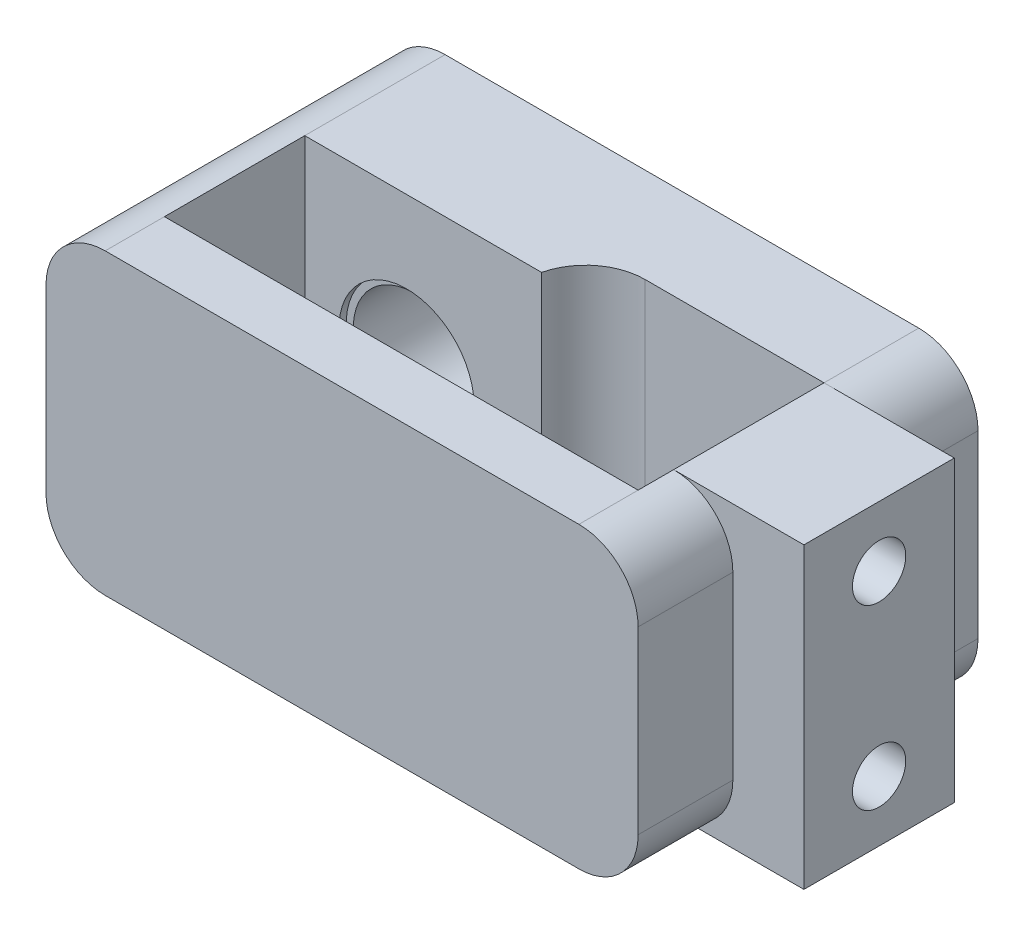
SolidWorks part; units mm, degrees
ref_plane "Front Plane" through (0, 0, 0) normal (0, 0, 1) x (1, 0, 0)
ref_plane "Top Plane" through (0, 0, 0) normal (0, 1, 0) x (1, 0, 0)
ref_plane "Right Plane" through (0, 0, 0) normal (1, 0, 0) x (0, 0, -1)
sketch "Sketch1" plane through (0, 0, 0) normal (0, 1, 0) x (1, 0, 0)
  line L1 (-20, 2.5) -> (20, 2.5)
  line L2 (-20, 2.5) -> (-20, -9.35)
  line L3 (-20, -9.35) -> (20, -9.35)
  line L4 (20, 2.5) -> (20, -9.35)
  line L7 (-25, 14.35) -> (25, 14.35)
  line L8 (-25, 14.35) -> (-25, -14.35)
  line L9 (-25, -14.35) -> (25, -14.35)
  line L10 (25, 14.35) -> (25, -14.35)
  point P0 (0, 0)
  point P6 (0, -9.35)
  point P7 (0, 0)
  point P12 (0, -14.35)
  point P13 (25, 0)
  dimension "D1" = 5
  dimension "D2" = 11.85
  dimension "D3" = 50
  dimension "D4" = 28.7
  dimension "D5" = 5
extrude "Boss-Extrude1" add sketch "Sketch1" along normal blind 25.2
sketch "Sketch4" plane through (0, 0, -2.5) normal (0, 0, 1) x (1, 0, 0)
  line L0 (-25, 25.2) -> (-25, 0) construction
  point P0 (-11.4, 12.6)
  point P7 (-25, 12.6)
  dimension "D1" = 13.6
sketch "Sketch9" plane through (20, 0, 0) normal (-1, 0, 0) x (0, 0, 1)
  line L0 (0, 20.1) -> (0, 5.1) construction
  line L2 (14.35, 25.2) -> (14.35, 0) construction
  point P0 (0, 20.1)
  point P2 (0, 5.1)
  point P11 (14.35, 12.6)
  point P12 (0, 12.6)
  dimension "D1" = 15
hole_wizard "Hole1" positions "Sketch4" profile "Sketch3" legacy end condition up to next
sketch "Sketch3" plane through (-11.4, 12.6, -2.5) normal (1, 0, 0) x (0, -1, 0)
  line L0 (0, 0) -> (0, 11.85)
  line L1 (0, 11.85) -> (5.1, 11.85)
  line L2 (5.1, 11.85) -> (5.1, 0.6)
  line L3 (5.1, 0.6) -> (5.7, 0.6)
  line L4 (5.7, 0.6) -> (5.7, 0)
  line L5 (5.7, 0) -> (0, 0)
  line L6 (0, 110) -> (0, -10) construction
  dimension "Diameter" = 10.2
  dimension "Depth" = 11.85
  dimension "C-Bore Diameter" = 11.4
  dimension "C-Bore Depth" = 0.6
sketch "Sketch10" plane through (25, 0, 0) normal (1, 0, 0) x (0, 0, -1)
  line L0 (-14.35, 25.2) -> (14.35, 25.2) construction
  line L1 (-6.35, 25.2) -> (6.35, 25.2)
  line L2 (-6.35, 25.2) -> (-6.35, 0)
  line L3 (-6.35, 0) -> (6.35, 0)
  line L4 (6.35, 25.2) -> (6.35, 0)
  line L5 (-14.35, 0) -> (14.35, 0) construction
  point P8 (0, 0)
  dimension "D1" = 12.7
extrude "Boss-Extrude2" add sketch "Sketch10" along normal blind 6
hole_wizard "M4 Clearance Hole1" positions "Sketch9" profile "Sketch8" hole size "M4" standard "ANSI Metric" end condition through all
sketch "Sketch8" plane through (20, 20.1, 0) normal (0, 1, 0) x (0, 0, 1)
  line L0 (0, 0) -> (0, 11)
  line L1 (0, 11) -> (2.25, 11)
  line L2 (2.25, 11) -> (2.25, 0.025)
  line L3 (2.25, 0.025) -> (2.275, 0)
  line L5 (2.275, 0) -> (0, 0)
  line L6 (-2.25, 0.025) -> (-2.275, 0) construction
  line L11 (0, -6.35) -> (0, 107.95) construction
  dimension "Thru Hole Dia." = 4.5
  dimension "Thru Hole Depth" = 11
  dimension "Near C'Sink Dia." = 4.55
  dimension "Near C'Sink Angle" = 90
sketch "Sketch11" plane through (0, 25.2, 0) normal (0, 1, 0) x (1, 0, 0)
  line L1 (20, 2.5) -> (0, 2.5)
  line L2 (20, 2.5) -> (20, 6.35)
  line L3 (20, 6.35) -> (0, 6.35)
  line L4 (0, 2.5) -> (0, 6.35)
extrude "Cut-Extrude1" cut sketch "Sketch11" against normal through all
fillet "Fillet1" radius 5 7 edges at (25, 0, -10.35) (25, 25.2, -10.35) (25, 0, 10.35) (25, 25.2, 10.35) (-25, 0, 0) (0, 12.6, -6.35) (-25, 25.2, 0)
